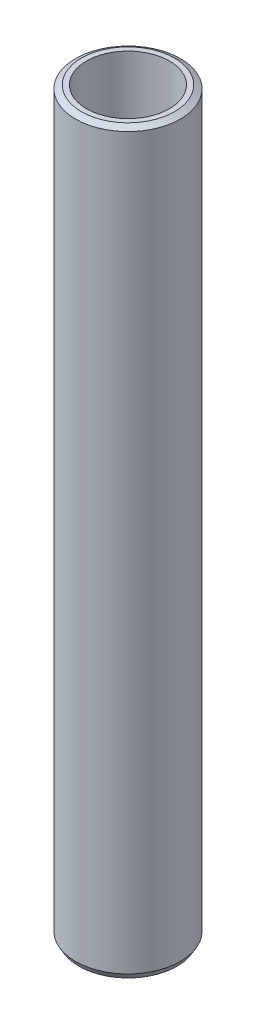
SolidWorks part; units mm, degrees
ref_plane "Front Plane" through (0, 0, 0) normal (0, 0, 1) x (1, 0, 0)
ref_plane "Top Plane" through (0, 0, 0) normal (0, 1, 0) x (1, 0, 0)
ref_plane "Right Plane" through (0, 0, 0) normal (1, 0, 0) x (0, 0, -1)
sketch "Sketch1" plane through (0, 0, 0) normal (0, 1, 0) x (1, 0, 0)
  circle A0 centre (0, 0) radius 35
  dimension "SHAFT_OD" = 70
extrude "Boss-Extrude1" add sketch "Sketch1" along normal blind 493.1456
sketch "Sketch2" plane through (0, 0, 0) normal (0, 1, 0) x (1, 0, 0)
  circle A0 centre (0, 0) radius 27.6499
  dimension "BORE_D" = 55.2998
extrude "Cut-Extrude1" cut sketch "Sketch2" along normal through all
chamfer "Chamfer1" distance 2.2837 angle 60 2 edges at (0, 493.1456, 35) (0, 0, 35) first distance on face at (0, 493.1456, 35) first distance on face at (0, 0, 27.6499)
